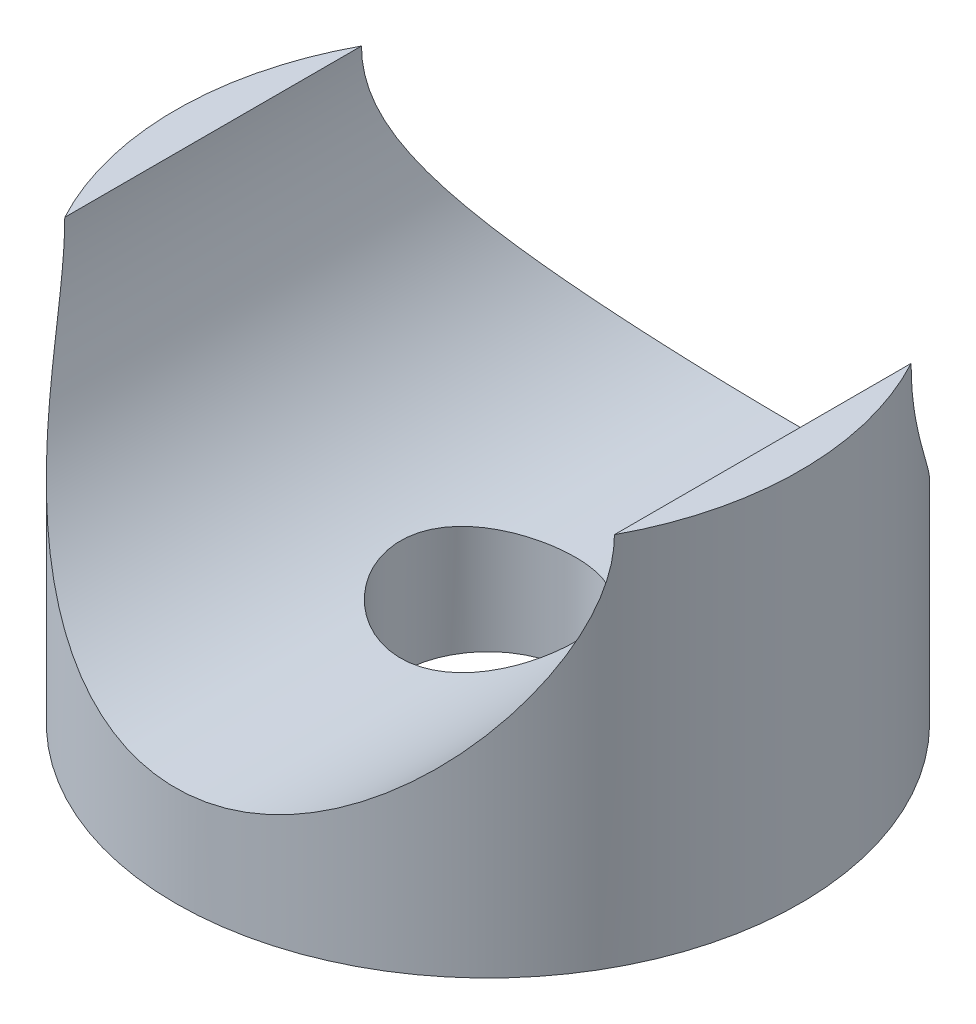
SolidWorks part; units mm, degrees
ref_plane "Front Plane" through (0, 0, 0) normal (0, 0, 1) x (1, 0, 0)
ref_plane "Top Plane" through (0, 0, 0) normal (0, 1, 0) x (1, 0, 0)
ref_plane "Right Plane" through (0, 0, 0) normal (1, 0, 0) x (0, 0, -1)
sketch "Sketch1" plane through (0, 0, 0) normal (0, 1, 0) x (1, 0, 0)
  circle A0 centre (0, 0) radius 12.5
  circle A1 centre (0, 0) radius 3.5
  dimension "D1" = 25
extrude "Boss-Extrude1" add sketch "Sketch1" along normal blind 15
sketch "Sketch2" plane through (0, 0, 0) normal (0, 0, 1) x (1, 0, 0)
  line L0 (12.5, 15) -> (-12.5, 15) construction
  circle A0 centre (0, 15) radius 11
  dimension "D1" = 22
extrude "Cut-Extrude1" cut sketch "Sketch2" against normal blind 22 and the other way blind 22
